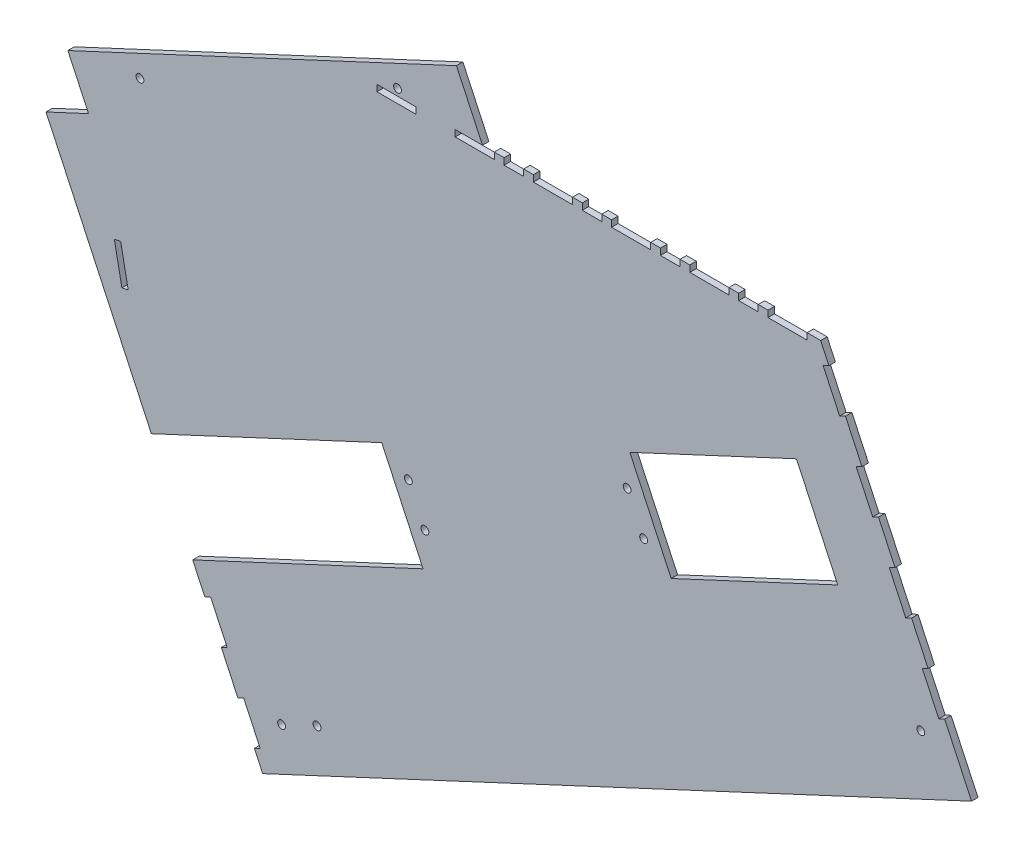
SolidWorks part; units mm, degrees
material "Balsa"
ref_plane "Front Plane" through (0, 0, 0) normal (0, 0, 1) x (1, 0, 0)
ref_plane "Top Plane" through (0, 0, 0) normal (0, 1, 0) x (1, 0, 0)
ref_plane "Right Plane" through (0, 0, 0) normal (1, 0, 0) x (0, 0, -1)
sketch "Sketch1" plane through (0, 0, 0) normal (0, 0, 1) x (1, 0, 0)
  line L0 (321.5462, 12.6346) -> (148.586, 12.6346)
  line L1 (148.586, 12.6346) -> (135.2566, 41.2196)
  line L2 (135.2566, 41.2196) -> (-63.4467, -51.4373)
  line L3 (-63.4467, -51.4373) -> (57.9293, -311.7289) construction
  line L4 (57.9293, -311.7289) -> (398.701, -152.8244)
  line L5 (271.5352, 119.8836) -> (277.3251, 107.4672) construction
  line L6 (190.5834, 136.311) -> (-12.0446, 41.824) construction
  line L7 (-63.4467, -51.4373) -> (255.5737, 97.3243) construction
  line L8 (398.701, -152.8244) -> (321.5462, 12.6346)
  line L9 (57.9293, -311.7289) -> (36.1779, -321.8717)
  line L10 (36.1779, -321.8717) -> (-74.6326, -84.2378)
  line L12 (-74.6326, -84.2378) -> (-52.8812, -74.095)
  line L13 (-90.9879, -49.1637) -> (-85.1981, -61.5801) construction
  line L14 (-52.8812, -74.095) -> (-63.4467, -51.4373)
  line L15 (73.956, 12.6346) -> (94.6178, 12.6346) construction
  line L19 (148.586, 12.6346) -> (135.2566, 41.2196) construction
  circle A0 centre (162.7613, -40.6644) radius 32.5 construction
  circle A1 centre (336.0773, -108.8767) radius 32.5 construction
  circle A2 centre (90.1802, -40.6644) radius 32.5 construction
  circle A3 centre (232.5481, -40.6644) radius 32.5 construction
  circle A4 centre (207.2768, 100.5118) radius 39.5 construction
  arc A5 (-3.3339, 41.4724) -> (-17.3744, 34.9252) centre (-8.0297, 33.2141) ccw construction
  circle A6 centre (304.5287, -40.6644) radius 32.5 construction
  circle A7 centre (254.9584, -108.8767) radius 32.5 construction
  circle A8 centre (179.3206, -108.8767) radius 32.5 construction
  circle A9 centre (101.4264, -108.8767) radius 32.5 construction
  circle A10 centre (270.383, -163.8108) radius 32.5 construction
  circle A11 centre (372.7594, -134.5783) radius 2
  dimension "D2" = 65
  dimension "D3" = 65
  dimension "D5" = 4
  dimension "D1" = 350
  dimension "D4" = 25
  dimension "24.5/2" = 15.8
  dimension "D6" = 27.5
extrude "Boss-Extrude1" add sketch "Sketch1" along normal up to surface (3.3 mm away)
sketch "Sketch2" plane through (0, 0, 3.3) normal (0, 0, 1) x (1, 0, 0)
  circle A0 centre (105.1447, 16.1444) radius 2
  circle A1 centre (-26.5934, -45.2861) radius 2
  circle A2 centre (-26.5934, -45.2861) radius 2 construction
  circle A3 centre (105.1447, 16.1444) radius 2 construction
extrude "Cut-Extrude1" cut sketch "Sketch2" against normal through all
sketch "Sketch3" plane through (0, 0, 3.3) normal (0, 0, 1) x (1, 0, 0)
  line L2 (398.701, -152.8244) -> (36.1779, -321.8717) construction
  line L3 (36.1779, -321.8717) -> (-74.6326, -84.2378) construction
  circle A0 centre (45.8517, -295.2932) radius 2
  circle A1 centre (63.9779, -286.8408) radius 2
  dimension "D1" = 4
  dimension "D2" = 4
  dimension "D3" = 20
  dimension "D5" = 20
  dimension "D6" = 20
  dimension "D4" = 20
extrude "Cut-Extrude2" cut sketch "Sketch3" against normal blind 4
sketch "Sketch4" plane through (0, 0, 3.3) normal (0, 0, 1) x (1, 0, 0)
  line L0 (330.2782, -91.2744) -> (309.1473, -45.959)
  line L1 (309.1473, -45.959) -> (223.9543, -85.6851)
  line L2 (223.9543, -85.6851) -> (245.0853, -131.0005)
  line L3 (245.0853, -131.0005) -> (330.2782, -91.2744)
  line L4 (309.1473, -45.959) -> (223.9543, -85.6851) construction
  line L5 (245.0853, -131.0005) -> (330.2782, -91.2744) construction
  line L6 (330.2782, -91.2744) -> (309.1473, -45.959) construction
  line L7 (118.2022, -190.1671) -> (97.0712, -144.8517)
  line L8 (97.0712, -144.8517) -> (-20.7488, -199.7921)
  line L9 (-20.7488, -199.7921) -> (0.3821, -245.1075)
  line L10 (0.3821, -245.1075) -> (118.2022, -190.1671)
  line L11 (118.2022, -190.1671) -> (0.3821, -245.1075) construction
  line L12 (-20.7488, -199.7921) -> (97.0712, -144.8517) construction
  line L13 (97.0712, -144.8517) -> (118.2022, -190.1671) construction
extrude "Cut-Extrude3" cut sketch "Sketch4" against normal blind 10
sketch "Sketch5" plane through (0, 0, 3.3) normal (0, 0, 1) x (1, 0, 0)
  circle A0 centre (231.009, -120.4069) radius 2
  circle A1 centre (222.5566, -102.2807) radius 2
  circle A2 centre (119.135, -172.5746) radius 2
  circle A3 centre (110.6826, -154.4484) radius 2
  circle A4 centre (119.135, -172.5746) radius 2 construction
  circle A7 centre (110.6826, -154.4484) radius 2 construction
  circle A8 centre (222.5566, -102.2807) radius 2 construction
  circle A9 centre (231.009, -120.4069) radius 2 construction
extrude "Cut-Extrude4" cut sketch "Sketch5" against normal blind 10
sketch "Sketch6" plane through (0, 0, 3.3) normal (0, 0, 1) x (1, 0, 0)
  line L0 (148.586, 12.6346) -> (321.5462, 12.6346) construction
  line L1 (314.6178, 12.6346) -> (294.6178, 12.6346)
  line L2 (314.6178, 12.6346) -> (314.6178, 9.3346)
  line L3 (314.6178, 9.3346) -> (294.6178, 9.3346)
  line L4 (294.6178, 12.6346) -> (294.6178, 9.3346)
  line L5 (314.6178, 12.6346) -> (294.6178, 9.3346) construction
  line L6 (314.6178, 9.3346) -> (294.6178, 12.6346) construction
  line L7 (314.6178, 9.3346) -> (314.6178, 12.6346) construction
  line L8 (274.6178, 9.3346) -> (254.6178, 9.3346)
  line L9 (254.6178, 12.6346) -> (254.6178, 9.3346)
  line L10 (274.6178, 12.6346) -> (274.6178, 9.3346)
  line L11 (274.6178, 12.6346) -> (254.6178, 12.6346)
  line L12 (234.6178, 9.3346) -> (214.6178, 9.3346)
  line L13 (214.6178, 12.6346) -> (214.6178, 9.3346)
  line L14 (234.6178, 12.6346) -> (234.6178, 9.3346)
  line L15 (234.6178, 12.6346) -> (214.6178, 12.6346)
  line L16 (194.6178, 9.3346) -> (174.6178, 9.3346)
  line L17 (174.6178, 12.6346) -> (174.6178, 9.3346)
  line L18 (194.6178, 12.6346) -> (194.6178, 9.3346)
  line L19 (194.6178, 12.6346) -> (174.6178, 12.6346)
  line L20 (154.6178, 9.3346) -> (134.6178, 9.3346)
  line L21 (134.6178, 12.6346) -> (134.6178, 9.3346)
  line L22 (154.6178, 12.6346) -> (154.6178, 9.3346)
  line L23 (154.6178, 12.6346) -> (134.6178, 12.6346)
  line L24 (114.6178, 9.3346) -> (94.6178, 9.3346)
  line L25 (94.6178, 12.6346) -> (94.6178, 9.3346)
  line L26 (114.6178, 12.6346) -> (114.6178, 9.3346)
  line L27 (114.6178, 12.6346) -> (94.6178, 12.6346)
  point P4 (304.6178, 10.9846)
  dimension "D1" = 3.3
  dimension "D2" = 20
  dimension "D3" = 6
extrude "Cut-Extrude5" cut sketch "Sketch6" against normal blind 10
sketch "Sketch7" plane through (0, 0, 3.3) normal (0, 0, 1) x (1, 0, 0)
  line L1 (325.7724, 3.5715) -> (322.7816, 2.1769)
  line L2 (325.7724, 3.5715) -> (334.2248, -14.5546)
  line L3 (334.2248, -14.5546) -> (331.2339, -15.9492)
  line L4 (322.7816, 2.1769) -> (331.2339, -15.9492)
  line L5 (325.7724, 3.5715) -> (331.2339, -15.9492) construction
  line L6 (334.2248, -14.5546) -> (322.7816, 2.1769) construction
  line L7 (322.7816, 2.1769) -> (331.2339, -15.9492) construction
  line L8 (334.2248, -14.5546) -> (342.6771, -32.6808) construction
  line L9 (331.2339, -15.9492) -> (334.2248, -14.5546) construction
  line L10 (321.5462, 12.6346) -> (398.701, -152.8244) construction
  line L11 (325.7724, 3.5715) -> (322.7816, 2.1769) construction
  line L12 (342.6771, -32.6808) -> (339.6863, -34.0754)
  line L13 (342.6771, -32.6808) -> (351.1295, -50.8069)
  line L14 (351.1295, -50.8069) -> (348.1387, -52.2016)
  line L15 (339.6863, -34.0754) -> (348.1387, -52.2016)
  line L16 (342.6771, -32.6808) -> (348.1387, -52.2016) construction
  line L17 (351.1295, -50.8069) -> (339.6863, -34.0754) construction
  line L18 (359.5819, -68.9331) -> (356.591, -70.3277)
  line L19 (359.5819, -68.9331) -> (368.0342, -87.0592)
  line L20 (368.0342, -87.0592) -> (365.0434, -88.4539)
  line L21 (356.591, -70.3277) -> (365.0434, -88.4539)
  line L22 (359.5819, -68.9331) -> (365.0434, -88.4539) construction
  line L23 (368.0342, -87.0592) -> (356.591, -70.3277) construction
  line L24 (376.4866, -105.1854) -> (373.4958, -106.58)
  line L25 (376.4866, -105.1854) -> (384.939, -123.3115)
  line L26 (384.939, -123.3115) -> (381.9481, -124.7062)
  line L27 (373.4958, -106.58) -> (381.9481, -124.7062)
  line L28 (376.4866, -105.1854) -> (381.9481, -124.7062) construction
  line L29 (384.939, -123.3115) -> (373.4958, -106.58) construction
  point P4 (330.6299, -10.0725)
  point P21 (347.5346, -46.3248)
  point P26 (364.4394, -82.5771)
  point P31 (381.3441, -118.8294)
  dimension "D1" = 4
extrude "Cut-Extrude6" cut sketch "Sketch7" against normal blind 10
sketch "Sketch8" plane through (0, 0, 3.3) normal (0, 0, 1) x (1, 0, 0)
  line L0 (148.586, 12.6346) -> (159.6178, 12.6346) construction
  line L1 (289.6178, 12.6346) -> (279.6178, 12.6346)
  line L2 (289.6178, 12.6346) -> (289.6178, 9.3346)
  line L3 (289.6178, 9.3346) -> (279.6178, 9.3346)
  line L4 (279.6178, 12.6346) -> (279.6178, 9.3346)
  line L5 (289.6178, 12.6346) -> (279.6178, 9.3346) construction
  line L6 (289.6178, 9.3346) -> (279.6178, 12.6346) construction
  line L7 (294.6178, 9.3346) -> (294.6178, 12.6346) construction
  line L8 (249.6178, 12.6346) -> (239.6178, 12.6346)
  line L9 (249.6178, 12.6346) -> (249.6178, 9.3346)
  line L10 (249.6178, 9.3346) -> (239.6178, 9.3346)
  line L11 (239.6178, 12.6346) -> (239.6178, 9.3346)
  line L12 (249.6178, 12.6346) -> (239.6178, 9.3346) construction
  line L13 (249.6178, 9.3346) -> (239.6178, 12.6346) construction
  line L14 (209.6178, 12.6346) -> (199.6178, 12.6346)
  line L15 (209.6178, 12.6346) -> (209.6178, 9.3346)
  line L16 (209.6178, 9.3346) -> (199.6178, 9.3346)
  line L17 (199.6178, 12.6346) -> (199.6178, 9.3346)
  line L18 (209.6178, 12.6346) -> (199.6178, 9.3346) construction
  line L19 (209.6178, 9.3346) -> (199.6178, 12.6346) construction
  line L20 (169.6178, 12.6346) -> (159.6178, 12.6346)
  line L21 (169.6178, 12.6346) -> (169.6178, 9.3346)
  line L22 (169.6178, 9.3346) -> (159.6178, 9.3346)
  line L23 (159.6178, 12.6346) -> (159.6178, 9.3346)
  line L24 (169.6178, 12.6346) -> (159.6178, 9.3346) construction
  line L25 (169.6178, 9.3346) -> (159.6178, 12.6346) construction
  point P4 (284.6178, 10.9846)
  point P14 (244.6178, 10.9846)
  point P19 (204.6178, 10.9846)
  point P24 (164.6178, 10.9846)
  dimension "D1" = 3.3
  dimension "D2" = 5
  dimension "D3" = 10
  dimension "D4" = 4
extrude "Cut-Extrude7" cut sketch "Sketch8" against normal blind 3.3
sketch "Sketch9" plane through (0, 0, 3.3) normal (0, 0, 1) x (1, 0, 0)
  line L0 (31.9517, -312.8086) -> (23.4994, -294.6825)
  line L1 (36.1779, -321.8717) -> (0.3821, -245.1075) construction
  line L2 (23.4994, -294.6825) -> (26.4902, -293.2878)
  line L3 (26.4902, -293.2878) -> (34.9425, -311.414)
  line L4 (34.9425, -311.414) -> (31.9517, -312.8086)
  line L5 (398.701, -152.8244) -> (36.1779, -321.8717) construction
  line L6 (15.047, -276.5563) -> (6.5946, -258.4302)
  line L7 (6.5946, -258.4302) -> (9.5855, -257.0355)
  line L8 (9.5855, -257.0355) -> (18.0378, -275.1617)
  line L9 (18.0378, -275.1617) -> (15.047, -276.5563)
  dimension "D1" = 3.3
  dimension "D2" = 20
  dimension "D3" = 10
  dimension "D4" = 2
extrude "Cut-Extrude8" cut sketch "Sketch9" against normal blind 3.3
sketch "Sketch10" plane through (0, 0, 3.3) normal (0, 0, 1) x (1, 0, 0)
  line L0 (-39.6914, -123.1134) -> (-35.8243, -142.7359)
  line L1 (-39.6914, -123.1134) -> (-36.4537, -122.4753)
  line L2 (-35.8243, -142.7359) -> (-32.5866, -142.0979)
  line L3 (-36.4537, -122.4753) -> (-32.5866, -142.0979)
  line L4 (-74.6326, -84.2378) -> (-52.8812, -74.095) construction
  line L5 (-44.9881, -96.237) -> (-39.6914, -123.1134) construction
  dimension "D1" = 20
  dimension "D2" = 50
  dimension "D3" = 3.3
extrude "Cut-Extrude9" cut sketch "Sketch10" against normal blind 3.3
